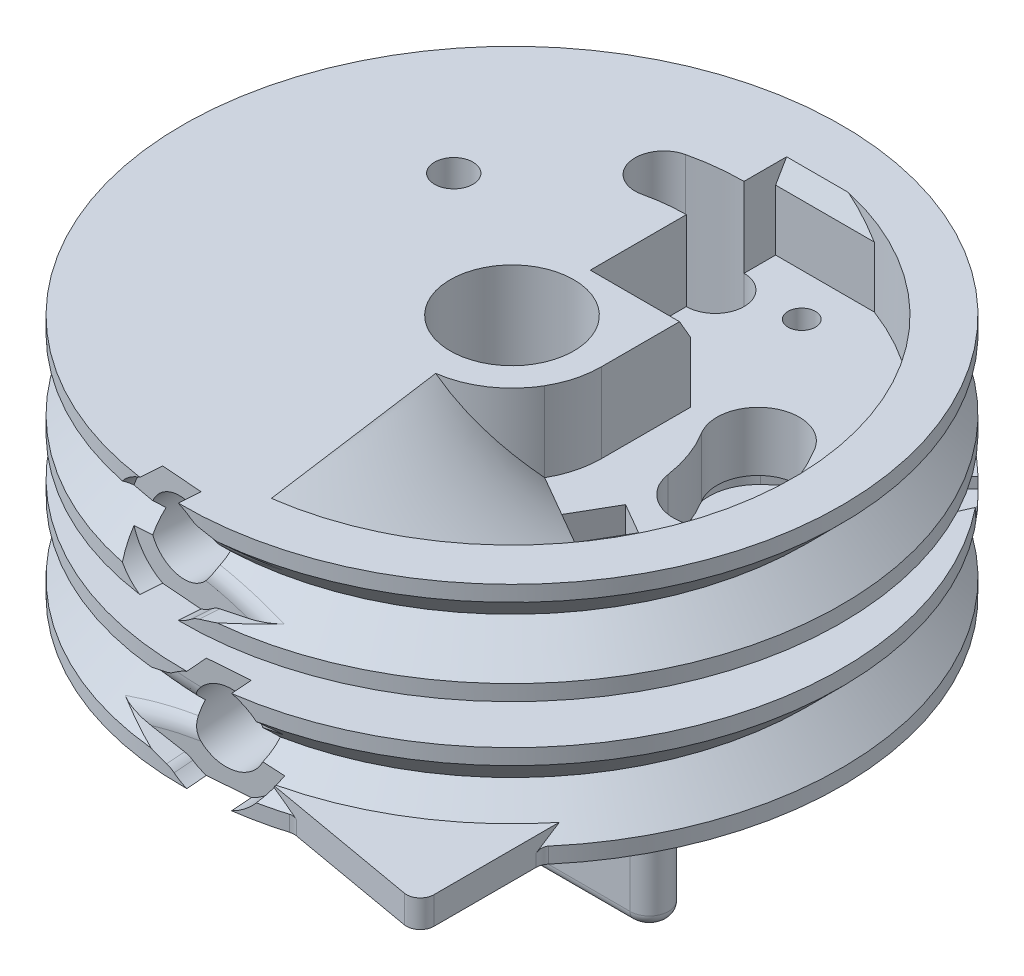
SolidWorks part; units mm, degrees
other "Fixed Pulley"
other "Floating Pulley" parameters "D1"=79.5609, "D2"=9.825, "D4"=9.808, "D5"=16.0705, "D8"=16.1048, "D9"=0.3468, "D3"=8.2373, "D6"=19.65, "D7"=19.65, "D10"=2.2, "D12"=39.3, "D13"=3.7963, "D14"=2.1845, "D11"=13.8
ref_plane "Front" through (0, 0, 0) normal (0, 0, 1) x (1, 0, 0)
ref_plane "Top" through (0, 0, 0) normal (0, 1, 0) x (1, 0, 0)
ref_plane "Right" through (0, 0, 0) normal (1, 0, 0) x (0, 0, -1)
sketch "Extension Spring Endpoints" plane through (0, 0, 0) normal (0, 1, 0) x (1, 0, 0)
  line L0 (0, 0) -> (14.3922, 13.3786) construction
  line L1 (0, 0) -> (0, 19.65) construction
  line L2 (0, 0) -> (-14.3922, 13.3786) construction
  line L3 (-14.3922, 13.3786) -> (-15.4176, 14.3317) construction
  line L4 (14.3922, 13.3786) -> (15.4176, 14.3317) construction
  line L5 (0, 0) -> (1.4985, -19.5928) construction
  line L6 (0, 0) -> (0, -19.65) construction
  line L7 (0, 0) -> (-1.4985, -19.5928) construction
  circle A0 centre (0, 0) radius 19.65 construction
  arc A1 (14.3922, 13.3786) -> (-14.3922, 13.3786) centre (0, 0) ccw
  arc A2 (-13.3668, 12.4254) -> (13.3668, 12.4254) centre (0, 0) cw
  arc A3 (-15.4176, 14.3317) -> (15.4176, 14.3317) centre (0, 0) cw
  arc A4 (-1.4985, -19.5928) -> (1.4985, -19.5928) centre (0, 0) ccw
  circle A5 centre (14.5948, 13.1573) radius 0.3
  circle A6 centre (-14.5948, 13.1573) radius 0.3
  dimension "D1" = 39.3
  dimension "D8" = 0.6
  dimension "D2" = 94.181
  dimension "D3" = 47.09
  dimension "D4" = 1.4
  dimension "D5" = 1.4
  dimension "D7" = 8.747
  dimension "D6" = 4.374
sketch "Sketch3" plane through (0, 0, 0) normal (0, 1, 0) x (1, 0, 0)
  circle A0 centre (0, 0) radius 20
  dimension "D1" = 40
sketch "Sketch4" plane through (0, 0, 0) normal (1, 0, 0) x (0, 0, -1)
  line L0 (0, 0) -> (-24, 0)
  line L1 (19.65, 0) -> (-19.65, 0) construction
  line L2 (-24, 0) -> (-24, 1.1387)
  line L3 (-24, 1.1387) -> (-21.4387, 3.7)
  line L4 (-21.4387, 3.7) -> (-24, 6.2613)
  line L5 (-24, 6.2613) -> (-24, 7.4)
  line L6 (-24, 7.4) -> (0, 7.4)
  line L7 (0, 7.4) -> (0, 0) construction
  line L8 (0, 0) -> (0, 7.4)
  circle A0 centre (-22, 3.7) radius 0.3969 construction
  point P16 (-24, 0.5694)
  dimension "D3" = 0.7937
  dimension "D1" = 44
  dimension "D2" = 7.4
  dimension "D4" = 90
  dimension "D5" = 2
revolve "Revolve1" add sketch "Sketch4" angle 360 about L7
sketch "Sketch5" plane through (0, 0, 0) normal (0, -1, 0) x (1, 0, 0)
  circle A0 centre (0, 0) radius 18.25
  arc A1 (-13.3668, -12.4254) -> (13.3668, -12.4254) centre (0, 0) ccw construction
extrude "Boss-Extrude1" add sketch "Sketch5" along normal blind 2.7
fillet "Fillet1" radius 1.4 1 edges at (0, 0, -18.25)
sketch "Sketch6" plane through (0, -2.7, 0) normal (0, -1, 0) x (1, 0, 0)
  line L0 (11.0852, -6.8433) -> (15.6552, -13.235) construction
  line L1 (15.6552, -13.235) -> (16.8359, -14.8863) construction
  line L2 (11.0852, -6.8433) -> (8.9913, -3.9149) construction
  line L3 (14.2731, -14.7218) -> (8.6341, -9.4801)
  line L4 (17.5091, -12.4081) -> (14.3729, -5.3769)
  line L5 (0, 0) -> (0, -19.65) construction
  line L6 (0, 0) -> (0, -19.65) construction
  line L7 (14.3922, -13.3786) -> (15.4176, -14.3317) construction
  line L8 (0, 0) -> (14.3922, -13.3786) construction
  line L9 (-17.5091, -12.4081) -> (-14.3729, -5.3769)
  line L10 (-14.2731, -14.7218) -> (-8.6341, -9.4801)
  circle A0 centre (11.0852, -6.8433) radius 3.6 construction
  circle A1 centre (15.6552, -13.235) radius 2.03 construction
  circle A2 centre (15.6552, -13.235) radius 0.965
  arc A3 (17.5091, -12.4081) -> (14.2731, -14.7218) centre (15.6552, -13.235) cw
  arc A4 (8.6341, -9.4801) -> (14.3729, -5.3769) centre (11.0852, -6.8433) cw
  circle A5 centre (11.0852, -6.8433) radius 1.55
  circle A10 centre (-11.0852, -6.8433) radius 1.55
  arc A11 (-8.6341, -9.4801) -> (-14.3729, -5.3769) centre (-11.0852, -6.8433) ccw
  arc A12 (-17.5091, -12.4081) -> (-14.2731, -14.7218) centre (-15.6552, -13.235) ccw
  circle A13 centre (-15.6552, -13.235) radius 0.965
  dimension "D1" = 7.2
  dimension "D2" = 4.06
  dimension "D3" = 13.4874
  dimension "D4" = 3.1
  dimension "D5" = 1.93
  dimension "D6" = 20.5
sketch "Sketch7" plane through (0, -2.7, 0) normal (0, -1, 0) x (1, 0, 0)
  line L0 (-14.2731, -14.7218) -> (-8.6341, -9.4801) construction
  line L4 (-14.2731, -14.7218) -> (-8.6341, -9.4801)
  line L6 (-14.3729, -5.3769) -> (-21.5642, -21.4994)
  line L7 (-21.5642, -21.4994) -> (-14.2731, -14.7218)
  line L8 (-17.5091, -12.4081) -> (-14.3729, -5.3769) construction
  arc A0 (-8.6341, -9.4801) -> (-14.3729, -5.3769) centre (-11.0852, -6.8433) ccw construction
  arc A1 (-8.6341, -9.4801) -> (-14.3729, -5.3769) centre (-11.0852, -6.8433) ccw
extrude "Cut-Extrude1" cut sketch "Sketch7" against normal offset from surface (3.5 mm away) 0.8 up to face at (0, 0, -19.65) offset beyond the face yes
sketch "Sketch8" plane through (0, 0.8, 0) normal (0, -1, 0) x (1, 0, 0)
  circle A0 centre (-11.0852, -6.8433) radius 1.4
  dimension "D1" = 2.8
extrude "Cut-Extrude2" cut sketch "Sketch8" against normal through all
sketch "Sketch9" plane through (0, -2.7, 0) normal (0, -1, 0) x (1, 0, 0)
  circle A0 centre (0, 0) radius 4.5
  dimension "D1" = 9
extrude "sleeve bearing bore" cut sketch "Sketch9" against normal through all
sketch "Sketch11" plane through (0, -2.7, 0) normal (0, -1, 0) x (1, 0, 0)
  line L1 (11.0852, -6.8433) -> (16.7205, -10.3222) construction
  line L2 (11.0852, -6.8433) -> (0, 0) construction
  line L3 (0, 0) -> (12.8888, -1.8946) construction
  line L5 (12.8888, -1.8946) -> (19.4411, -2.8577) construction
  circle A0 centre (0, 0) radius 9.4273 construction
  arc A1 (-8.6341, -9.4801) -> (-14.3729, -5.3769) centre (-11.0852, -6.8433) ccw construction
  circle A4 centre (11.0852, -6.8433) radius 1.55 construction
  circle A7 centre (0, 0) radius 24.9495 construction
  circle A9 centre (0, 0) radius 19.65 construction
  arc A10 (16.7205, -10.3222) -> (19.4411, -2.8577) centre (0, 0) ccw construction
  arc A12 (12.8888, -1.8946) -> (11.0852, -6.8433) centre (0, 0) cw construction
  arc A13 (13.6379, -8.4192) -> (15.857, -2.3309) centre (0, 0) ccw
  arc A14 (8.5324, -5.2674) -> (9.9207, -1.4583) centre (0, 0) ccw
  arc A15 (8.5324, -5.2674) -> (13.6379, -8.4192) centre (11.0852, -6.8433) ccw
  arc A16 (15.857, -2.3309) -> (9.9207, -1.4583) centre (12.8888, -1.8946) ccw
  point P1 (12.2397, -4.4611)
  dimension "D1" = 23.327
  dimension "D3" = 3
  dimension "D2" = 13.0273
extrude "screw head pocket" cut sketch "Sketch11" against normal through all
ref_plane "Plane3" through (-1.8303, 0, 23.9301) normal (-0.0763, 0, 0.9971) x (0.9971, 0, 0.0763)
ref_plane "Plane6" through (0, 0, 0) normal (-0.0763, 0, 0.9971) x (0.9971, 0, 0.0763)
sketch "Sketch30" plane through (0, 0, 0) normal (-0.0763, 0, 0.9971) x (0.9971, 0, 0.0763)
  line L0 (0, 3.7) -> (-22, 3.7) construction
  line L1 (21.4387, 3.7) -> (-21.4387, 3.7) construction
  line L2 (-24, 6.2613) -> (-24, 1.1387)
  line L3 (24, 6.2613) -> (-24, 6.2613) construction
  line L4 (24, 1.1387) -> (-24, 1.1387) construction
  line L5 (-24, 6.2613) -> (-22.5969, 6.2613)
  line L6 (-22.5969, 6.2613) -> (-22.5969, 1.1387)
  line L7 (-22.5969, 1.1387) -> (-24, 1.1387)
  line L8 (-22.3969, 3.2113) -> (-22.3969, 4.1887) construction
  circle A0 centre (-22, 3.7) radius 0.3969 construction
  point P16 (-22.3969, 3.7)
  dimension "D1" = 0.7937
  dimension "D2" = 22
  dimension "D3" = 0.2
revolve "Wire Rope Capture" [suppressed] add sketch "Sketch30" angle 10 about L8
sketch "Sketch15" plane through (-1.8303, 0, 23.9301) normal (-0.0763, 0, 0.9971) x (0.9971, 0, 0.0763)
  line L0 (21.4387, 3.7) -> (-21.4387, 3.7) construction
  circle A0 centre (0, 3.7) radius 4
  dimension "D1" = 8
extrude "Wire Rope Cinch" cut sketch "Sketch15" against normal blind 1.6
sketch "Sketch16" plane through (-1.7083, 0, 22.3348) normal (-0.0763, 0, 0.9971) x (0.9971, 0, 0.0763)
  circle A0 centre (0, 3.7) radius 2.55
  dimension "D1" = 5.1
extrude "Heat Set Insert Hole" cut sketch "Sketch16" against normal blind 7
ref_plane "Plane1" through (0, -2.9, 0) normal (0, -1, 0) x (-1, 0, 0)
ref_plane "Center Plane" through (0, -1.45, 0) normal (0, -1, 0) x (-1, 0, 0)
sketch "Limit Switch Constraints" plane through (0, 7.4, 0) normal (0, 1, 0) x (1, 0, 0)
  line L0 (0, 19.2) -> (6.5, 19.2)
  line L1 (0, 19.2) -> (0, 6.5)
  line L2 (6.5, 19.2) -> (6.5, 6.5)
  line L3 (0, 6.5) -> (6.5, 6.5)
  line L4 (0, 14.8) -> (0, 0) construction
  line L9 (-1.8682, 14.6048) -> (0, 0) construction
  circle A0 centre (0, 0) radius 6.5
  circle A1 centre (0, 0) radius 4.5 construction
  circle A2 centre (0, 14.8) radius 0.6
  circle A4 centre (5, 9.6) radius 1.1
  circle A5 centre (5, 16.1) radius 1.1
  arc A6 (0, 14.8) -> (-3.3561, 14.4145) centre (0, 0) ccw construction
  arc A7 (0, 16.9) -> (-3.8323, 16.4598) centre (0, 0) ccw
  arc A8 (0, 12.7) -> (-2.8799, 12.3692) centre (0, 0) ccw
  arc A9 (0, 12.7) -> (0, 16.9) centre (0, 14.8) ccw
  arc A10 (-3.8323, 16.4598) -> (-2.8799, 12.3692) centre (-3.3561, 14.4145) ccw
  circle A11 centre (-3.3561, 14.4145) radius 1.5 construction
  point P16 (-1.6891, 14.7033)
  dimension "D4" = 1.2
  dimension "D8" = 2.2
  dimension "D14" = 3
  dimension "D2" = 12.7
  dimension "D3" = 6.5
  dimension "D5" = 8.3
  dimension "D6" = 1.5
  dimension "D7" = 3.1
  dimension "D9" = 3.1
  dimension "D10" = 1.5
  dimension "D11" = 14.8
  dimension "D13" = 7.29
  dimension "D12" = 0.6
sketch "Sketch33" plane through (0, -2.7, 0) normal (0, -1, 0) x (1, 0, 0)
  arc A0 (-2.8799, -12.3692) -> (0, -12.7) centre (0, 0) ccw construction
  arc A1 (-2.8799, -12.3692) -> (0, -12.7) centre (0, 0) ccw
  arc A2 (-2.8799, -12.3692) -> (-3.8323, -16.4598) centre (-3.3561, -14.4145) ccw construction
  arc A3 (-2.8799, -12.3692) -> (-3.8323, -16.4598) centre (-3.3561, -14.4145) ccw
  arc A4 (-3.8323, -16.4598) -> (0, -16.9) centre (0, 0) ccw construction
  arc A5 (-3.8323, -16.4598) -> (0, -16.9) centre (0, 0) ccw
  arc A6 (0, -16.9) -> (0, -12.7) centre (0, -14.8) ccw construction
  arc A7 (0, -16.9) -> (0, -12.7) centre (0, -14.8) ccw
extrude "Limit Switch Slot" cut sketch "Sketch33" against normal through all
sketch "Sketch34" plane through (0, 7.4, 0) normal (0, 1, 0) x (1, 0, 0)
  line L0 (0, 6.5) -> (0, 12.7)
  line L2 (5.6292, -3.25) -> (17.7535, -10.25)
  line L3 (0, 16.9) -> (0, 19.2)
  line L5 (0, 19.2) -> (7.184, 19.2)
  line L6 (0, 19.2) -> (6.5, 19.2) construction
  line L7 (5.6292, -3.25) -> (0, 0) construction
  line L8 (0, 0) -> (0, -9.0359) construction
  arc A0 (0, 6.5) -> (5.6292, -3.25) centre (0, 0) cw
  circle A1 centre (0, 0) radius 6.5 construction
  arc A2 (0, 12.7) -> (-2.8799, 12.3692) centre (0, 0) ccw construction
  arc A3 (0, 12.7) -> (-2.8799, 12.3692) centre (0, 0) ccw
  arc A4 (0, 16.9) -> (-3.8323, 16.4598) centre (0, 0) ccw construction
  arc A5 (-3.8323, 16.4598) -> (-2.8799, 12.3692) centre (-3.3561, 14.4145) ccw construction
  arc A6 (0, 16.9) -> (-3.8323, 16.4598) centre (0, 0) ccw
  arc A7 (-3.8323, 16.4598) -> (-2.8799, 12.3692) centre (-3.3561, 14.4145) ccw
  arc A9 (7.184, 19.2) -> (17.7535, -10.25) centre (0, 0) cw
  dimension "D1" = 20.5
  dimension "D2" = 60
extrude "Limit Switch Pocket" cut sketch "Sketch34" against normal blind 5.8
sketch "Sketch35" plane through (0, 1.6, 0) normal (0, 1, 0) x (1, 0, 0)
  circle A0 centre (5, 16.1) radius 1
  circle A1 centre (5, 9.6) radius 1 construction
  dimension "D1" = 2
extrude "Limit Switch Holes" cut sketch "Sketch35" against normal through all
sketch "Sketch37" plane through (0, 1.6, 0) normal (0, 1, 0) x (1, 0, 0)
  circle A0 centre (0, 0) radius 6.5
curve "Helix/Spiral1" pitch 40 height 32 radius 6.5 left hand yes centre (0, 1.6, 0) axis (0, 1, 0) start towards (0.866, 0, 0.5)
sketch "Sketch36" plane through (0, 0, 0) normal (0.5, 0, -0.866) x (-0.866, 0, -0.5)
  line L4 (-6.5, 7.4) -> (-20.5, 7.4)
  line L5 (-20.5, 7.4) -> (-20.5, 1.6)
  line L6 (-20.5, 1.6) -> (-6.5, 1.6)
  line L7 (-6.5, 1.6) -> (-6.5, 7.4)
  line L8 (-6.5, 7.4) -> (-20.5, 7.4)
  line L9 (-20.5, 7.4) -> (-20.5, 1.6)
  line L10 (-20.5, 1.6) -> (-6.5, 1.6)
  line L11 (-6.5, 1.6) -> (-6.5, 7.4)
  dimension "D1" = 0
sweep "Wire Ramp" cut profiles "Sketch36" path "Helix/Spiral1" align with end faces yes
sketch "Sketch38" plane through (0, 1.6, 0) normal (0, 1, 0) x (1, 0, 0)
  line L0 (10.8253, -6.25) -> (12.5253, -3.3055)
  line L1 (10.8253, -6.25) -> (8.5737, -4.95)
  line L2 (12.5253, -3.3055) -> (10.2737, -2.0055)
  line L3 (8.5737, -4.95) -> (10.2737, -2.0055)
  line L4 (5.6292, -3.25) -> (17.7535, -10.25) construction
  line L5 (11.6913, -6.75) -> (13.0578, -4.3832) construction
  line L6 (14.2574, -4.3055) -> (16.509, -5.6055)
  line L7 (14.809, -8.55) -> (16.509, -5.6055)
  line L8 (12.5574, -7.25) -> (14.809, -8.55)
  line L9 (12.5574, -7.25) -> (14.2574, -4.3055)
  dimension "D1" = 3.4
  dimension "D2" = 1
  dimension "D3" = 2.6
extrude "Cut-Extrude17" cut sketch "Sketch38" against normal through all
sketch "Sketch39" plane through (0, -2.7, 0) normal (0, -1, 0) x (1, 0, 0)
  line L0 (12.5574, 7.25) -> (10.8253, 6.25)
  line L1 (12.5574, 7.25) -> (14.2574, 4.3055)
  line L2 (10.8253, 6.25) -> (12.5253, 3.3055)
  line L3 (14.2574, 4.3055) -> (12.5253, 3.3055)
extrude "Cut-Extrude18" cut sketch "Sketch39" against normal offset from surface (2.5 mm away) 1.8 up to face at (5, 1.6, -15.1)
fillet "Fillet2" radius 1 2 edges at (13.4074, -0.2, 5.7778) (11.6753, -0.2, 4.7778)
sketch "Sketch41" plane through (0, 1.6, 0) normal (0, 1, 0) x (1, 0, 0)
  line L0 (0, 6.5) -> (6.5, 6.5) construction
  line L1 (0, 6.5) -> (6.5, 6.5)
  line L2 (6.5, 6.5) -> (6.5, 0)
  arc A0 (0, 6.5) -> (6.5, 0) centre (0, 0) cw
  circle A1 centre (0, 0) radius 6.5 construction
extrude "Boss-Extrude2" add sketch "Sketch41" along normal up to surface (5.8 mm away) up to face at (-0.8532, 7.4, 11.1554)
chamfer "Chamfer2" distance 0.8 angle 60 2 edges at (3.25, 7.4, -6.5) (3.592, 7.4, -19.2) first distance on face at (-0.8532, 7.4, 11.1554)
sketch "Sketch12" plane through (0, -1.45, 0) normal (0, -1, 0) x (-1, 0, 0)
  line L0 (0, 0) -> (0, -22) construction
  line L1 (0, -24) -> (0, 0) construction
sketch "Sketch13" plane through (0, 0, 0) normal (1, 0, 0) x (0, 0, -1)
  line L0 (0, -1.45) -> (-22, -1.45) construction
  line L1 (0, -1.45) -> (-22, -1.45) construction
  line L2 (-24, 6.2613) -> (-24, 7.4) construction
  line L3 (-21.4387, 3.7) -> (-24, 6.2613) construction
  line L4 (-24, 1.1387) -> (-21.4387, 3.7) construction
  line L5 (-24, 0) -> (-24, 1.1387) construction
  line L7 (-24, 7.4) -> (0, 7.4) construction
  line L8 (0, 0) -> (0, 7.4) construction
  line L9 (-24, 6.2613) -> (-24, 7.4) construction
  line L10 (-21.4387, 3.7) -> (-24, 6.2613) construction
  line L11 (-24, 1.1387) -> (-21.4387, 3.7) construction
  line L12 (-24, 0) -> (-24, 1.1387) construction
  line L13 (0, 0) -> (-24, 0) construction
  line L14 (-24, 7.4) -> (0, 7.4) construction
  line L15 (0, 0) -> (0, 7.4) construction
  line L16 (0, 0) -> (-24, 0) construction
  line L17 (0, -2.9) -> (0, -10.3)
  line L18 (-24, -10.3) -> (0, -10.3)
  line L19 (-24, -9.1613) -> (-24, -10.3)
  line L20 (-21.4387, -6.6) -> (-24, -9.1613)
  line L21 (-24, -4.0387) -> (-21.4387, -6.6)
  line L22 (-24, -2.9) -> (-24, -4.0387)
  line L23 (0, -2.9) -> (-24, -2.9)
revolve "Revolve2" add sketch "Sketch13" angle 360 about L17
sketch "Sketch19" plane through (0, -10.3, 0) normal (0, -1, 0) x (1, 0, 0)
  circle A0 centre (0, 0) radius 3.1
  dimension "D1" = 6.2
extrude "Cut-Extrude9" cut sketch "Sketch19" against normal up to next (7.4 mm away)
ref_plane "Plane4" through (1.8303, 0, 23.9301) normal (0.0763, 0, 0.9971) x (0.9971, 0, -0.0763)
sketch "Sketch42" plane through (0, -10.3, 0) normal (0, -1, 0) x (1, 0, 0)
  line L0 (18, 15.8745) -> (18, 24.8745)
  line L1 (18, 24.8745) -> (7.0447, 22.9428)
  line L2 (18, 15.8745) -> (18, 14.571)
  line L3 (7.0447, 22.9428) -> (5.0751, 22.5955)
  arc A0 (18, 14.571) -> (5.0751, 22.5955) centre (0, 0) ccw
  circle A3 centre (0, 0) radius 24 construction
  circle A5 centre (0, 0) radius 3.1 construction
  dimension "D1" = 18
  dimension "D2" = 9
  dimension "D4" = 2
  dimension "D3" = 80
extrude "home switch tab" add sketch "Sketch42" against normal blind 2
sketch "Sketch17" plane through (1.8303, 0, 23.9301) normal (0.0763, 0, 0.9971) x (0.9971, 0, -0.0763)
  line L0 (21.4387, -6.6) -> (-21.4387, -6.6) construction
  circle A0 centre (0, -6.6) radius 4
  dimension "D1" = 8
extrude "Cut-Extrude7" cut sketch "Sketch17" against normal blind 1.6
sketch "Sketch18" plane through (1.7083, 0, 22.3348) normal (0.0763, 0, 0.9971) x (0.9971, 0, -0.0763)
  circle A0 centre (0, -6.6) radius 2.55
  dimension "D1" = 5.1
extrude "Cut-Extrude8" cut sketch "Sketch18" against normal blind 7
sketch "Sketch21" plane through (0, -2.9, 0) normal (0, -1, 0) x (1, 0, 0)
  circle A0 centre (0, 0) radius 9.575
  dimension "D1" = 19.15
extrude "Cut-Extrude13" cut sketch "Sketch21" along normal blind 5
hole_wizard "M3 Clearance Hole1" positions "Sketch23" profile "Sketch24" hole size "M3" standard "ANSI Metric" end condition through all
sketch "Sketch23" plane through (0, -10.3, 0) normal (0, -1, 0) x (-1, 0, 0)
  line L9 (0, 0) -> (-6.4927, 0) construction
  line L12 (0, 0) -> (-4.4901, -4.4901) construction
  line L13 (0, 0) -> (4.4901, -4.4901) construction
  line L16 (0, 0) -> (4.4901, 4.4901) construction
  line L19 (0, 0) -> (-4.4901, 4.4901) construction
  point P73 (-4.4901, -4.4901)
  point P83 (4.4901, -4.4901)
  point P90 (4.4901, 4.4901)
  point P98 (-4.4901, 4.4901)
  dimension "D1" = 45
  dimension "D2" = 6.35
sketch "Sketch24" plane through (4.4901, -10.3, -4.4901) normal (1, 0, 0) x (0, 0, -1)
  line L0 (0, 0) -> (0, 23.5364)
  line L1 (0, 23.5364) -> (1.7, 23.5364)
  line L2 (1.7, 23.5364) -> (1.7, 0)
  line L5 (1.7, 0) -> (0, 0)
  line L11 (0, -6.35) -> (0, 107.95) construction
  dimension "Thru Hole Dia." = 3.4
  dimension "Thru Hole Depth" = 23.5364
ref_plane "Set Screw Plane" through (0, 0, -24) normal (0, 0, -1) x (-1, 0, 0)
sketch "Sketch25" plane through (0, 0, -24) normal (0, 0, -1) x (-1, 0, 0)
  line L0 (9.575, -2.9) -> (-9.575, -2.9) construction
  line L1 (0, -5.4) -> (0, -2.9) construction
  circle A0 centre (0, -5.4) radius 1.7
  dimension "D1" = 3.4
  dimension "D2" = 2.5
extrude "Set Screw Hole" cut sketch "Sketch25" against normal up to surface (14.425 mm away) up to face at (0, -7.9, -9.575)
sketch "Sketch26" plane through (0, -2.9, 0) normal (0, 1, 0) x (1, 0, 0)
  line L0 (14.3729, 5.3769) -> (21.5642, 21.4994)
  line L4 (21.5642, 21.4994) -> (8.6341, 9.4801)
  line L5 (14.2731, 14.7218) -> (8.6341, 9.4801) construction
  line L6 (17.5091, 12.4081) -> (14.3729, 5.3769) construction
  arc A2 (8.6341, 9.4801) -> (14.3729, 5.3769) centre (11.0852, 6.8433) ccw construction
  arc A3 (8.6341, 9.4801) -> (14.3729, 5.3769) centre (11.0852, 6.8433) ccw
extrude "Cut-Extrude15" cut sketch "Sketch26" against normal blind 0.8
sketch "Sketch27" plane through (0, -3.7, 0) normal (0, 1, 0) x (1, 0, 0)
  circle A0 centre (11.0852, 6.8433) radius 1.4
  dimension "D1" = 2.8
extrude "Cut-Extrude16" cut sketch "Sketch27" against normal through all
fillet "Fillet3" radius 1 3 edges at (18, -9.3, 24.8745) (18, -9.7306, 15.8745) (7.0447, -9.7306, 22.9428)
sketch "Sketch43" plane through (-1.7083, 0, 22.3348) normal (-0.0763, 0, 0.9971) x (0.9971, 0, 0.0763)
  line L0 (10, 4.7) -> (10, 2.7)
  line L1 (10, 4.7) -> (0, 7.4)
  line L2 (-1.5199, 7.4) -> (1.5199, 7.4) construction
  line L5 (10, 3.7) -> (0, 3.7) construction
  line L6 (0, 0) -> (0, 7.4)
  line L7 (21.4387, 3.7) -> (-21.4387, 3.7) construction
  line L8 (10, 2.7) -> (0, 0)
  dimension "D1" = 2
  dimension "D2" = 10
extrude "Cut-Extrude20" cut sketch "Sketch43" along normal through all
fillet "Fillet4" radius 1.6 4 edges at (2.2803, 2.3844, 22.6398) (0.8976, 0.7206, 23.2618) (0.8976, 6.6794, 23.2618)
sketch "Sketch44" plane through (1.7083, 0, 22.3348) normal (0.0763, 0, 0.9971) x (0.9971, 0, -0.0763)
  line L0 (0, -6.6) -> (-10, -6.6) construction
  line L1 (0.4317, -6.6) -> (-21.4387, -6.6) construction
  line L2 (-10, -7.6) -> (-10, -5.6)
  line L3 (-10, -5.6) -> (0, -2.9)
  line L4 (-1.5199, -2.9) -> (1.5199, -2.9) construction
  line L5 (0, -2.9) -> (0, -10.3)
  line L6 (-10, -7.6) -> (0, -10.3)
  dimension "D1" = 10
  dimension "D2" = 2
extrude "Cut-Extrude21" cut sketch "Sketch44" along normal through all
fillet "Fillet5" radius 1.6 4 edges at (-0.8976, -9.5794, 23.2618) (-0.8976, -3.6206, 23.2618)
sketch "Sketch40" [suppressed] plane through (0, -2.9, 0) normal (0, 1, 0) x (1, 0, 0)
  circle A0 centre (-3.3561, 14.4145) radius 1.425
  dimension "D1" = 2.85
extrude "Cut-Extrude19" [suppressed] cut sketch "Sketch40" against normal through all
chamfer "Chamfer1" [suppressed] distance 4 angle 5
sketch "Sketch45" plane through (0, -10.3, 0) normal (0, -1, 0) x (1, 0, 0)
  line L0 (2.3688, 6.6114) -> (-6.6114, -2.3688)
  line L1 (-2.3688, -6.6114) -> (6.6114, 2.3688)
  circle A0 centre (4.4901, 4.4901) radius 3 construction
  circle A1 centre (-4.4901, -4.4901) radius 3 construction
  circle A2 centre (-4.4901, 4.4901) radius 3 construction
  circle A3 centre (4.4901, -4.4901) radius 3 construction
  arc A4 (6.6114, 2.3688) -> (2.3688, 6.6114) centre (4.4901, 4.4901) ccw
  arc A5 (-2.3688, -6.6114) -> (-6.6114, -2.3688) centre (-4.4901, -4.4901) cw
  circle A6 centre (4.4901, 4.4901) radius 1.6
  circle A7 centre (-4.4901, -4.4901) radius 1.6
  dimension "D1" = 6
  dimension "D2" = 3.2
extrude "Boss-Extrude3" add sketch "Sketch45" along normal blind 3 separate body
sketch "Sketch46" plane through (0, -13.3, 0) normal (0, -1, 0) x (1, 0, 0)
  line L0 (-10, 0) -> (10, 0) construction
  line L1 (-10, 1.4) -> (10, 1.4)
  line L2 (-10, -1.4) -> (10, -1.4)
  arc A0 (-10, 1.4) -> (-10, -1.4) centre (-10, 0) ccw
  arc A1 (10, -1.4) -> (10, 1.4) centre (10, 0) ccw
  point P2 (0, 0)
  dimension "D1" = 2.8
  dimension "D2" = 20
extrude "Boss-Extrude4" add sketch "Sketch46" along normal blind 12
fillet "Fillet6" radius 3 2 edges at (1.4, -13.3, 1.4) (-1.4, -13.3, -1.4)
sketch "Sketch47" plane through (0, -13.3, 0) normal (0, -1, 0) x (1, 0, 0)
  circle A0 centre (-4.4901, -4.4901) radius 3
  circle A1 centre (4.4901, 4.4901) radius 3
  arc A2 (-7.4888, -4.4) -> (-2.3688, -6.6114) centre (-4.4901, -4.4901) ccw construction
  arc A3 (7.4888, 4.4) -> (2.3688, 6.6114) centre (4.4901, 4.4901) ccw construction
extrude "Cut-Extrude22" cut sketch "Sketch47" along normal through all
fillet "Fillet7" radius 0.8 4 edges at (-11.4, -25.3, 0) (0, -25.3, 1.4) (11.4, -25.3, 0) (0, -25.3, -1.4)
chamfer "Chamfer5" distance 3 angle 45 2 edges at (4.2426, -13.3, 0) (-4.2426, -13.3, 0)
delete or keep bodies "Body-Delete/Keep 1" [suppressed] type keep bodies bodies 129
delete or keep bodies "Body-Delete/Keep 2" [suppressed] type keep bodies bodies 126
chamfer "Chamfer3" [suppressed] distance 1.6 angle 8
chamfer "Chamfer4" [suppressed] distance 1.6 angle 8
delete or keep bodies "Body-Delete/Keep 3" [suppressed] type keep bodies bodies 133
equation "\"D2@Extension Spring Endpoints\"=( \"Ext Spring Total Length\" - (2*\"Ext Spring Wire Diameter\") + \"prestretch\" )  /  ( \"nominal_spring_arc_diameter\" / 2 )  *  ( 180 /3.14159)"
equation "\"D3@Extension Spring Endpoints\" = \"D2@Extension Spring Endpoints\" / 2"
equation "\"Ext Spring Diameter\"= 2.8mm"
equation "\"D4@Extension Spring Endpoints\"=\"Ext Spring Diameter\"/2"
equation "\"D5@Extension Spring Endpoints\"=\"D4@Extension Spring Endpoints\""
equation "\"Ext Spring Total Length\"= 33mm"
equation "\"Ext Spring Hook Length\"= 2.5mm"
equation "\"Ext Spring Extension\"= 2mm"
equation "\"Ext Spring Wire Diameter\"= 0.6mm"
equation "\"wire_rope_diameter\"= 0.79375"
equation "\"D3@Sketch4\"=\"wire_rope_diameter\""
equation "\"D1@Boss-Extrude1\"=\"Ext Spring Diameter\" - \"shim_thickness\" + .1"
equation "\"shim_thickness\"= 0.2mm"
equation "\"D1@Fillet1\"=\"Ext Spring Diameter\"/2"
equation "\"D7@Extension Spring Endpoints\"= (\"Ext Spring Extension\" + 1)/(\"D1@Extension Spring Endpoints\"/2)*(180/3.14159)"
equation "\"D6@Extension Spring Endpoints\"=\"D7@Extension Spring Endpoints\"/2"
equation "\"nominal_pulley_diameter\"= 44"
equation "\"D1@Sketch4\"=\"nominal_pulley_diameter\""
equation "\"D1@Sketch30\"=\"wire_rope_diameter\""
equation "\"D2@Sketch30\"=\"nominal_pulley_diameter\"/2"
equation "\"D9@Limit Switch Constraints\" = \"D7@Limit Switch Constraints\""
equation "\"D10@Limit Switch Constraints\" = \"D6@Limit Switch Constraints\""
equation "\"D13@Limit Switch Constraints\" = \"stretch_angle\""
equation "\"nominal_spring_arc_diameter\"=39.3"
equation "\"D1@Extension Spring Endpoints\"=\"nominal_spring_arc_diameter\""
equation "\"stretch_angle\"= ( \"Ext Spring Extension\" + \"prestretch\" ) / ( \"nominal_spring_arc_diameter\" / 2 ) * ( 180 / 3.14159 )"
equation "\"prestretch\"= 0.5"
equation "\"D8@Extension Spring Endpoints\"=\"Ext Spring Wire Diameter\""
